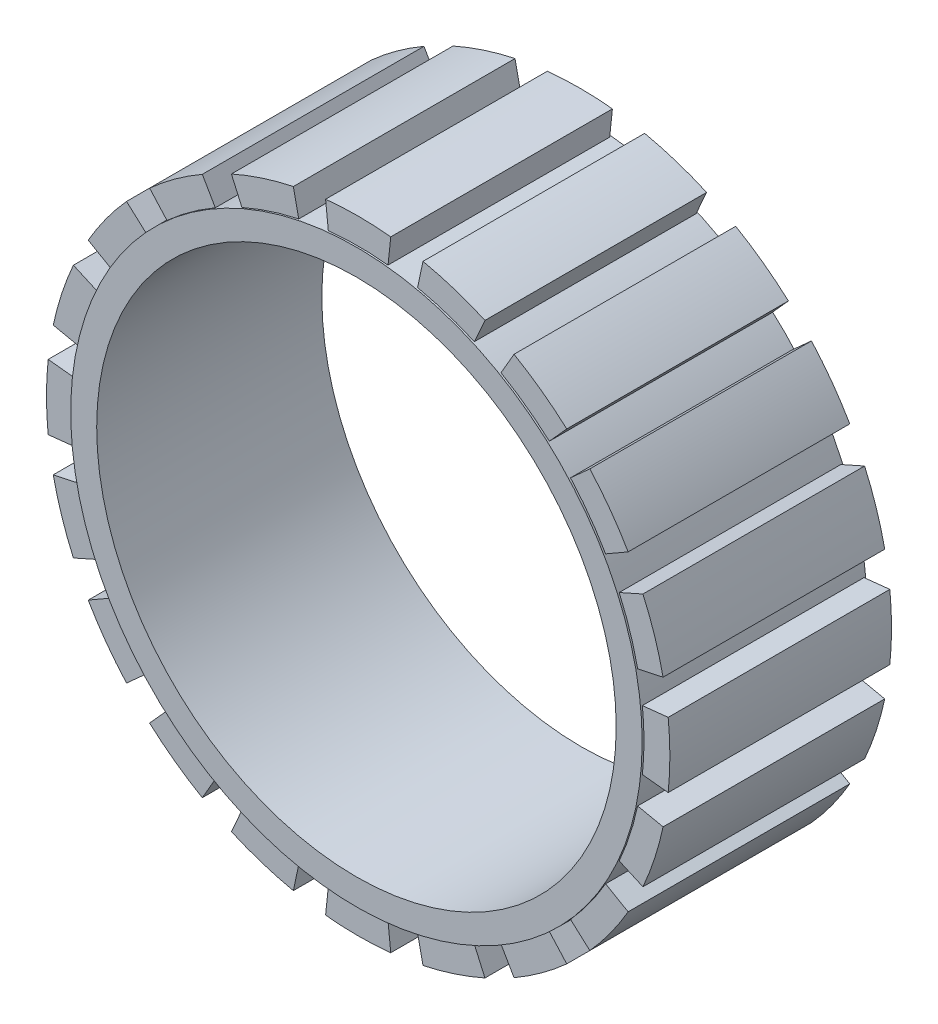
SolidWorks part; units mm, degrees
ref_plane "Front Plane" through (0, 0, 0) normal (0, 0, 1) x (1, 0, 0)
ref_plane "Top Plane" through (0, 0, 0) normal (0, 1, 0) x (1, 0, 0)
ref_plane "Right Plane" through (0, 0, 0) normal (1, 0, 0) x (0, 0, -1)
sketch "Sketch1" plane through (0, 0, 0) normal (0, 0, 1) x (1, 0, 0)
  circle A0 centre (0, 0) radius 15
  circle A1 centre (0, 0) radius 16.5
  dimension "D1" = 30
  dimension "D2" = 1.5
extrude "Boss-Extrude1" add sketch "Sketch1" along normal blind 13
ref_plane "Plane1" through (0, 0, 0.1) normal (0, 0, -1) x (-1, 0, 0)
sketch "Sketch2" plane through (0, 0, 0.1) normal (0, 0, -1) x (-1, 0, 0)
  line L0 (0, 0) -> (0, 15) construction
  line L1 (0, 0) -> (2.5812, 16.2969) construction
  line L2 (0, 0) -> (-2.5812, 16.2969) construction
  line L3 (-1.8815, 17.9014) -> (-1.7247, 16.4096)
  line L4 (1.8815, 17.9014) -> (1.7247, 16.4096)
  circle A0 centre (0, 0) radius 16.5 construction
  circle A1 centre (0, 0) radius 16.5 construction
  arc A2 (-1.7247, 16.4096) -> (1.7247, 16.4096) centre (0, 0) cw
  arc A3 (-1.8815, 17.9014) -> (1.8815, 17.9014) centre (0, 0) cw
  circle A4 centre (0, 0) radius 15 construction
  point P9 (-1.544, 16.4276)
  point P11 (0, 15)
  dimension "D3" = 1.5
  dimension "D1" = 18
  dimension "D2" = 6
extrude "Boss-Extrude3" add sketch "Sketch2" against normal offset from surface (12.8 mm away) 0.1 up to face at (16.5, 0, 13)
ref_axis "Axis1" through (0, 0, 13) along (0, 0, -1)
pattern_circular "CirPattern1" count 20 over 360 about axis through (0, 0, 13) along (0, 0, -1) of "Boss-Extrude3"
